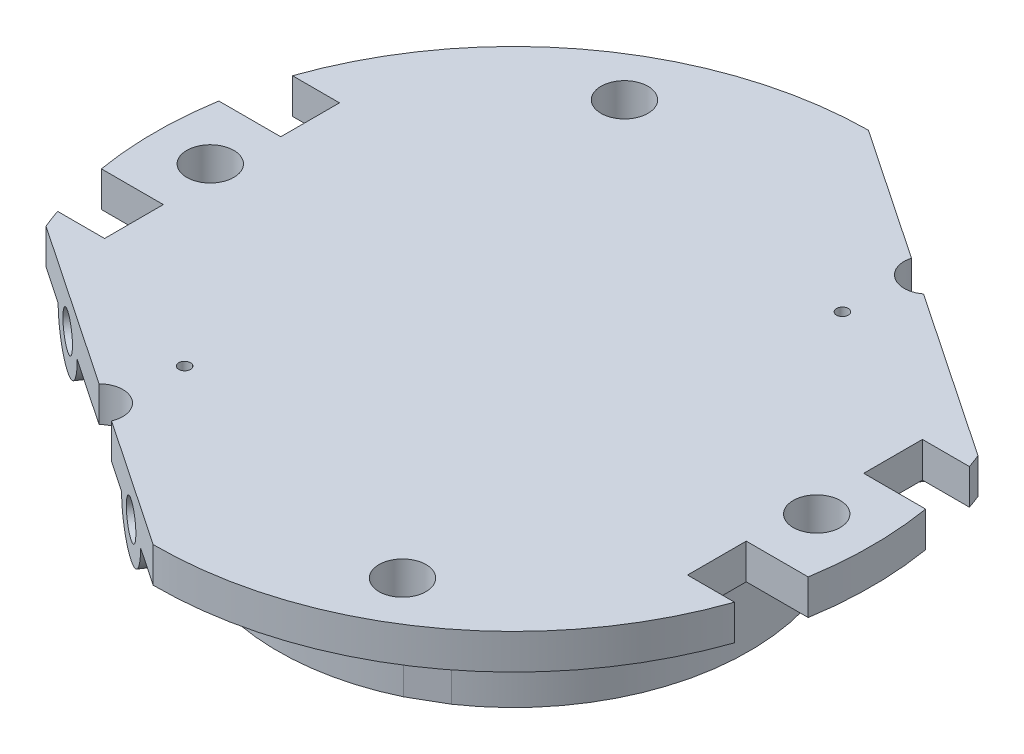
SolidWorks part; units mm, degrees
ref_plane "Alzado" through (0, 0, 0) normal (0, 0, 1) x (1, 0, 0)
ref_plane "Planta" through (0, 0, 0) normal (0, 1, 0) x (1, 0, 0)
ref_plane "Vista lateral" through (0, 0, 0) normal (1, 0, 0) x (0, 0, -1)
sketch "Croquis1" plane through (0, 0, 0) normal (0, 1, 0) x (1, 0, 0)
  circle A0 centre (0, 0) radius 30.5
extrude "Saliente-Extruir1" add sketch "Croquis1" along normal blind 3
sketch "Croquis5" plane through (0, 3, 0) normal (0, 1, 0) x (1, 0, 0)
  line L1 (28.8141, -5) -> (30.0874, -5)
  line L2 (28.8141, 5) -> (30.0874, 5)
  line L3 (-24.8141, 10) -> (-28.8141, 10)
  line L4 (24.8141, -5) -> (24.8141, -10)
  line L5 (-24.8141, -10) -> (-28.8141, -10)
  line L6 (24.8141, -5) -> (28.8141, -5)
  line L7 (24.8141, 5) -> (24.8141, 10)
  line L8 (-24.8141, 5) -> (-28.8141, 5)
  line L9 (-24.8141, 5) -> (-24.8141, 10)
  line L10 (-24.8141, -5) -> (-28.8141, -5)
  line L11 (-24.8141, -5) -> (-24.8141, -10)
  line L12 (24.8141, 5) -> (28.8141, 5)
  line L13 (24.8141, -10) -> (28.8141, -10)
  line L14 (24.8141, 10) -> (28.8141, 10)
  line L15 (-28.8141, 5) -> (-30.0874, 5)
  line L16 (-28.8141, -5) -> (-30.0874, -5)
  line L18 (-24.8141, 0) -> (-12.407, -21.4896)
  line L19 (-12.407, -21.4896) -> (12.407, -21.4896)
  line L20 (12.407, -21.4896) -> (24.8141, 0)
  line L21 (24.8141, 0) -> (12.407, 21.4896)
  line L22 (12.407, 21.4896) -> (-12.407, 21.4896)
  line L23 (-12.407, 21.4896) -> (-24.8141, 0)
  circle A0 centre (0, 0) radius 21.4896 construction
  circle A1 centre (0, 0) radius 30.5 construction
  arc A2 (-28.8141, 10) -> (-30.0874, 5) centre (0, 0) ccw
  arc A4 (-30.0874, -5) -> (-28.8141, -10) centre (0, 0) ccw
  arc A5 (30.0874, -5) -> (28.8141, -10) centre (0, 0) cw
  arc A6 (28.8141, 10) -> (30.0874, 5) centre (0, 0) cw
  circle M2 centre (0, 0) radius 30.5
extrude "Cortar-Extruir3" cut sketch "Croquis5" against normal blind 4 contours L10 L16 L5 L11 M2 | L15 L8 L9 L3 M2 | L14 L7 L12 L2 M2 | L4 L13 L1 L6 M2 region at (27.1844, 3, 7.3876) region at (-27.1844, 3, 7.3876) region at (27.1844, 3, -7.3876) region at (-27.1844, 3, -7.3876)
sketch "Croquis7" plane through (0, 3, 0) normal (0, 1, 0) x (1, 0, 0)
  line L2 (25.8141, 0) -> (12.907, 22.3556)
  line L3 (12.907, 22.3556) -> (-12.907, 22.3556)
  line L4 (-12.907, 22.3556) -> (-25.8141, 0)
  line L5 (-25.8141, 0) -> (-12.907, -22.3556)
  line L6 (-12.907, -22.3556) -> (12.907, -22.3556)
  line L7 (12.907, -22.3556) -> (25.8141, 0)
  circle A0 centre (25.8141, 0) radius 2
  circle A4 centre (-25.8141, 0) radius 2
  circle A5 centre (0, 0) radius 22.3556 construction
  circle A6 centre (12.907, 22.3556) radius 2
  circle A7 centre (-12.907, -22.3556) radius 2
  circle A8 centre (-12.907, 22.3556) radius 2
  circle A9 centre (12.907, -22.3556) radius 2
extrude "Cortar-Extruir4" cut sketch "Croquis7" against normal blind 10 contours A8 L4 L3 | A4 L4 L5 | A4 L5 L4 | A8 L3 L4 | L2 A6 L3 | L3 A6 L2 | L7 A0 L2 | L2 A0 L7 | A7 L5 L6 | A7 L6 L5 | L6 A9 L7 | L7 A9 L6 | A4 region at (24.7114, 3, 0) region at (26.3654, 3, 0) region at (12.3557, 3, -21.4007) region at (13.1827, 3, -22.8331) region at (13.1827, 3, 22.8331) region at (12.3557, 3, 21.4007) region at (-12.3557, 3, -21.4007) region at (-13.1827, 3, -22.8331) region at (-13.1827, 3, 22.8331) region at (-12.3557, 3, 21.4007) region at (-24.7114, 3, 0) region at (-26.3654, 3, 0)
sketch "Croquis8" plane through (0, 3, 0) normal (0, 1, 0) x (1, 0, 0)
  line L0 (0, 0) -> (12, 0)
  line L1 (12, 0) -> (12, 16)
  line L2 (0, 0) -> (-12, 0)
  line L3 (-12, 0) -> (-12, -16)
  circle A0 centre (12, 16) radius 0.5
  circle A1 centre (-12, -16) radius 0.5
extrude "Cortar-Extruir5" cut sketch "Croquis8" against normal blind 3 contours A1 | A0 region at (11.6564, 3, -16.3436) region at (-11.6564, 3, 15.6564)
sketch "Croquis9" plane through (0, 3, 0) normal (0, 1, 0) x (1, 0, 0)
  line L2 (-10, 17.3205) -> (-8.701, 18.0705)
  line L5 (25.6318, 16.5306) -> (27.1318, 13.9325)
  line L6 (-10, 17.3205) -> (-11.299, 16.5705)
  line L8 (10, -17.3205) -> (8.701, -18.0705)
  line L9 (10, -17.3205) -> (11.299, -16.5705)
  circle A0 centre (0, 0) radius 20.0562
  circle A1 centre (-12, -16) radius 3
  circle A2 centre (12, 16) radius 3
extrude "Saliente-Extruir2" add sketch "Croquis9" against normal blind 13 contours L2 L6 | L8 L9 region at (0, 3, 0)
sketch "Croquis11" plane through (14.0495, 0, -20.8293) normal (0.5592, 0, -0.829) x (-0.829, 0, -0.5592)
  line L1 (17.2916, 0) -> (-17.2916, 0)
  line L2 (17.2916, 0) -> (17.2916, 3)
  line L3 (17.2916, 3) -> (-17.2916, 3)
  line L4 (-17.2916, 0) -> (-17.2916, 3)
extrude "Saliente-Extruir3" add sketch "Croquis11" along normal blind 6
sketch "Croquis12" plane through (0, 3, 0) normal (0, 1, 0) x (1, 0, 0)
  circle A0 centre (12.907, 22.3556) radius 2
extrude "Cortar-Extruir7" cut sketch "Croquis12" against normal blind 3
sketch "Croquis13" plane through (17.4047, 0, -25.8035) normal (0.5592, 0, -0.829) x (-0.829, 0, -0.5592)
  line L0 (-17.2916, 0) -> (17.2916, 0)
  line L1 (17.2916, 3) -> (-17.2916, 3)
  line L2 (17.2916, 3) -> (-17.2916, 3) construction
  line L3 (17.2916, 0) -> (17.2916, 3) construction
  circle A1 centre (10, 0) radius 3
  circle A2 centre (-10, 0) radius 3
  circle A3 centre (10, 0) radius 1.5
  circle A5 centre (-10, 0) radius 1.5
  line M4 (-17.2916, 0) -> (17.2916, 0)
extrude "Saliente-Extruir4" add sketch "Croquis13" against normal blind 20 contours A3 L0 A1 | A3 L0 A1 | A5 L0 A2 | A5 L0 A2 | A5 M4 | A3 M4 region at (25.6951, 1.5671, -20.2116) region at (25.6951, -0.6366, -20.2116) region at (23.8297, -0.0671, -21.4698) region at (10.8337, 2.0739, -30.2358) region at (10.9797, -0.0671, -30.1373) region at (9.1143, -0.6366, -31.3955)
sketch "Croquis14" plane through (17.4047, 0, -25.8035) normal (0.5592, 0, -0.829) x (-0.829, 0, -0.5592)
  circle A0 centre (-10, 0) radius 1.5
  circle A1 centre (10, 0) radius 1.5
extrude "Cortar-Extruir8" cut sketch "Croquis14" against normal blind 6
sketch "Croquis15" plane through (0, 3, 0) normal (0, 1, 0) x (1, 0, 0)
  line L0 (28.3849, 11.16) -> (-0.2859, 30.4987)
  line L1 (28.3849, 11.16) -> (0.1409, -30.7136)
  line L2 (-0.2859, 30.4987) -> (-28.5299, -11.3749)
  line L3 (0.1409, -30.7136) -> (-28.5299, -11.3749)
  circle A0 centre (-0.2859, 0) radius 30.7165
  arc M12 (-28.8141, -10) -> (28.8141, -10) centre (0, 0) ccw
  circle M28 centre (-12.907, -22.3556) radius 2
extrude "Cortar-Extruir9" cut sketch "Croquis15" against normal blind 3 contours L3 M12 M28 region at (-15.494, 3, 22.7434)
sketch "Croquis16" plane through (-14.1945, 0, 21.0442) normal (-0.5592, 0, 0.829) x (0.829, 0, 0.5592)
  line L0 (-16.9088, 0) -> (-16.9088, 3)
  line L1 (-16.9088, 0) -> (16.78, 0)
  line L2 (-16.9088, 3) -> (16.78, 3)
  line L3 (16.78, 0) -> (16.78, 3)
extrude "Saliente-Extruir5" add sketch "Croquis16" along normal blind 6
sketch "Croquis17" plane through (0, 3, 0) normal (0, 1, 0) x (1, 0, 0)
  circle A0 centre (-12.907, -22.3556) radius 2
extrude "Cortar-Extruir10" cut sketch "Croquis17" against normal blind 3
sketch "Croquis18" plane through (-17.5497, 0, 26.0185) normal (-0.5592, 0, 0.829) x (0.829, 0, 0.5592)
  line L2 (-16.9088, 0) -> (16.78, 0) construction
  circle A0 centre (9.9356, 0) radius 3
  circle A1 centre (-10.0644, 0) radius 3
extrude "Saliente-Extruir6" add sketch "Croquis18" against normal blind 25
sketch "Croquis19" plane through (-17.5497, 0, 26.0185) normal (-0.5592, 0, 0.829) x (0.829, 0, 0.5592)
  circle A0 centre (-10.0644, 0) radius 1.5
  circle A1 centre (9.9356, 0) radius 1.5
extrude "Cortar-Extruir11" cut sketch "Croquis19" against normal blind 5
sketch "Croquis20" plane through (17.4047, 0, -25.8035) normal (0.5592, 0, -0.829) x (-0.829, 0, -0.5592)
  line L0 (17.2916, 3) -> (17.2916, 0)
  line L1 (17.2916, 0) -> (13, 0)
  line L2 (-7, 0) -> (7, 0) construction
  line L3 (7, 0) -> (-7, 0)
  line L4 (-13, 0) -> (-17.2916, 0)
  line L5 (-17.2916, 0) -> (-17.2916, 3)
  line L6 (-17.2916, 3) -> (17.2916, 3)
  arc A0 (13, 0) -> (7, 0) centre (10, 0) cw
  arc A1 (7, 0) -> (13, 0) centre (10, 0) ccw construction
  arc A2 (-7, 0) -> (-13, 0) centre (-10, 0) cw
extrude "Cortar-Extruir12" cut sketch "Croquis20" against normal blind 6
sketch "Croquis21" plane through (-17.5497, 0, 26.0185) normal (-0.5592, 0, 0.829) x (0.829, 0, 0.5592)
  line L0 (-13.0644, 0) -> (-16.9088, 0)
  line L1 (-16.9088, 0) -> (-16.9088, 3)
  line L2 (-16.9088, 3) -> (16.78, 3)
  line L3 (16.78, 3) -> (16.78, 0)
  line L4 (16.78, 0) -> (12.9356, 0)
  line L5 (6.9356, 0) -> (-7.0644, 0)
  arc A0 (-13.0644, 0) -> (-7.0644, 0) centre (-10.0644, 0) ccw
  arc A1 (6.9356, 0) -> (12.9356, 0) centre (9.9356, 0) ccw
extrude "Cortar-Extruir13" cut sketch "Croquis21" against normal blind 6
sketch "Croquis22" plane through (-14.1945, 0, 21.0442) normal (-0.5592, 0, 0.829) x (0.829, 0, 0.5592)
  circle A0 centre (-10.0644, 0) radius 1.5
  circle A1 centre (9.9356, 0) radius 1.5
extrude "Cortar-Extruir14" cut sketch "Croquis22" against normal blind 6
sketch "Croquis23" plane through (14.0495, 0, -20.8293) normal (0.5592, 0, -0.829) x (-0.829, 0, -0.5592)
  circle A0 centre (-10, 0) radius 1.5
  circle A1 centre (10, 0) radius 1.5
extrude "Cortar-Extruir15" cut sketch "Croquis23" against normal blind 6
